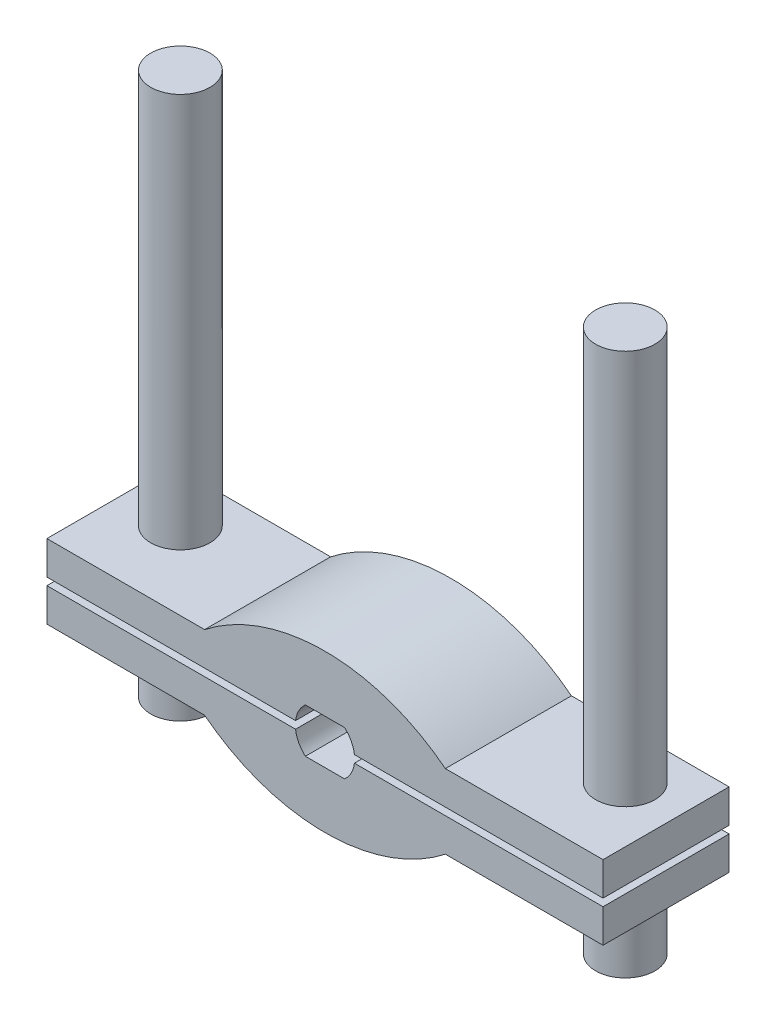
SolidWorks part; units mm, degrees
note: The reader was unsure of these and kept them because the rebuilt part matched: shared geometry of "Эскиз3<2>".
material "AISI 1020"
ref_plane "Спереди" through (0, 0, 0) normal (0, 0, 1) x (1, 0, 0)
ref_plane "Сверху" through (0, 0, 0) normal (0, 1, 0) x (1, 0, 0)
ref_plane "Справа" through (0, 0, 0) normal (1, 0, 0) x (0, 0, -1)
sketch "Эскиз1" plane through (0, 0, 0) normal (0, 0, 1) x (1, 0, 0)
  line L0 (-267.3267, 36.4) -> (267.3267, 36.4) construction
  line L2 (0, 36.4) -> (0, 6) construction
  line L4 (0, 21.2) -> (0, 6)
  line L5 (-7.9373, 1) -> (-75, 1)
  line L7 (-32.4695, 10) -> (-75, 10)
  line L8 (-75, 1) -> (-75, 10)
  line L9 (-5.2915, 6) -> (5.2915, 6) construction
  line L10 (-1000, 0) -> (49000, 0) construction
  line L11 (0, -6) -> (-5.2915, -6)
  line L12 (-5.2915, -6) -> (5.2915, -6)
  line L13 (5.2915, 6) -> (-5.2915, 6)
  line L15 (0, 6) -> (-5.2915, 6)
  line L16 (0, -21.2) -> (0, -6)
  line L17 (-32.4695, -10) -> (-75, -10)
  line L18 (-75, -1) -> (-75, -10)
  line L19 (-7.9373, -1) -> (-75, -1)
  arc A1 (0, 21.2) -> (-32.4695, 10) centre (0, -31.4655) ccw
  arc A2 (0, -21.2) -> (-32.4695, -10) centre (0, 31.4655) cw
  arc A3 (-5.2915, -6) -> (-7.9373, -1) centre (0, 0) cw
  arc A4 (5.2915, -6) -> (5.2915, 6) centre (0, 0) ccw
  arc A5 (-5.2915, 6) -> (-5.2915, -6) centre (0, 0) ccw
  arc A7 (-5.2915, 6) -> (-7.9373, 1) centre (0, 0) ccw
  point P10 (0, 0)
  point P16 (-41.4686, 1)
  point P28 (0, 0)
  point P29 (0, 0)
  dimension "D1" = 75
  dimension "D2" = 1
  dimension "D3" = 9
  dimension "D4" = 0
extrude "Бобышка-Вытянуть1" add sketch "Эскиз1" against normal up to surface (34 mm away)
sketch "Эскиз3" plane through (0, 10, 0) normal (0, 1, 0) x (1, 0, 0)
  circle A0 centre (-60, 21) radius 8 construction
  circle A1 centre (-60, 21) radius 8
extrude "Бобышка-Вытянуть2" add sketch "Эскиз3" along normal offset from surface (106.4 mm away) 40 offset beyond the face yes
cosmetic thread "Условное изображение резьбы2" parameters "D1"=20, "D2"=14.344
extrude "Бобышка-Вытянуть3" add sketch "Эскиз3<2>" against normal blind 40
sketch "Эскиз3<2>" plane through (0, 10, 0) normal (0, 1, 0) x (1, 0, 0) same geometry as "Эскиз3"
cosmetic thread "Условное изображение резьбы1" parameters "D1"=25, "D2"=14.344
sketch "Эскиз4" plane through (0, -10, 0) normal (0, -1, 0) x (1, 0, 0)
  circle A2 centre (-60, -21) radius 8.25
  circle A3 centre (-60, -21) radius 8.25
  dimension "D1" = 0.25
extrude "Вырез-Вытянуть1" cut sketch "Эскиз4" against normal up to surface (9 mm away) up to face at (-41.4686, -1, -17)
mirror "Зеркальное отражение1" about plane through (0, -21.2, -111.6726) normal (1, 0, 0) of bodies 106 107 105
other "Сохранить тела1"
